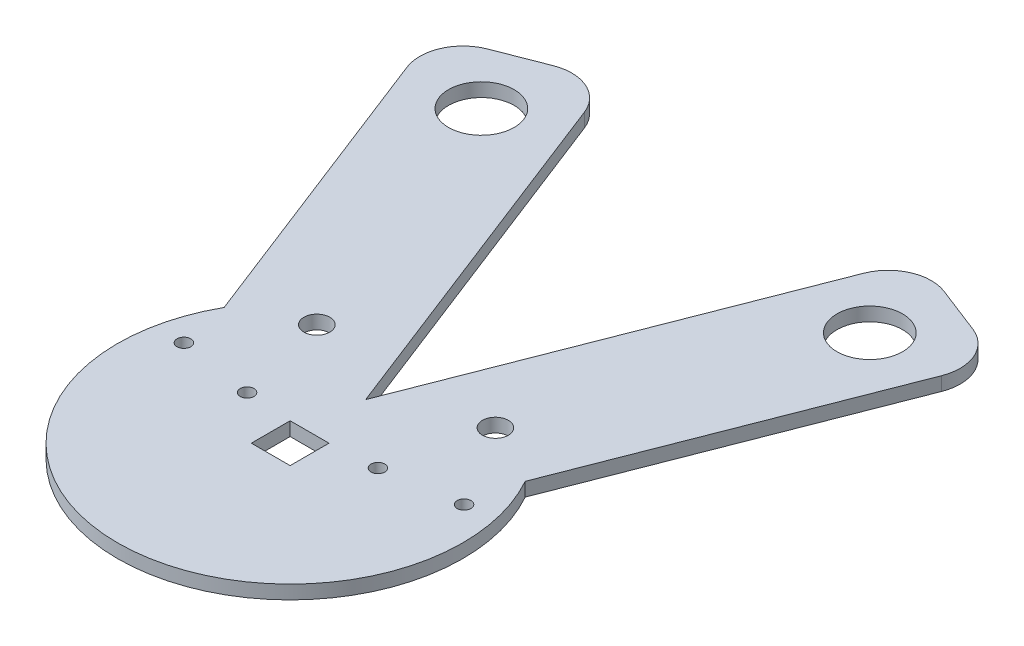
SolidWorks part; units mm, degrees
ref_plane "Front Plane" through (0, 0, 0) normal (0, 0, 1) x (1, 0, 0)
ref_plane "Top Plane" through (0, 0, 0) normal (0, 1, 0) x (1, 0, 0)
ref_plane "Right Plane" through (0, 0, 0) normal (1, 0, 0) x (0, 0, -1)
sketch "Sketch1" plane through (0, 0, 0) normal (0, 1, 0) x (1, 0, 0)
  line L0 (-45, 89.3029) -> (45, 89.3029) construction
  line L1 (-4.5, -4.5) -> (4.5, -4.5)
  line L2 (-4.5, -4.5) -> (-4.5, 4.5)
  line L3 (-4.5, 4.5) -> (4.5, 4.5)
  line L4 (4.5, -4.5) -> (4.5, 4.5)
  line L5 (-4.5, -4.5) -> (4.5, 4.5) construction
  line L6 (-4.5, 4.5) -> (4.5, -4.5) construction
  line L7 (-65.5537, 98.3347) -> (-23.6685, -9.2175)
  line L8 (23.6685, -9.2175) -> (65.5537, 98.3347)
  line L9 (-35.9681, 109.8566) -> (0, 17.4983)
  line L10 (0, 17.4983) -> (35.9681, 109.8566)
  line L11 (35.9681, 109.8566) -> (65.5537, 98.3347)
  line L12 (-65.5537, 98.3347) -> (-35.9681, 109.8566)
  line L13 (-51.0505, 104.8392) -> (-33.4783, 59.7176) construction
  line L14 (-4.9398, -38.9318) -> (18139.7128, 46552.608) construction
  line L15 (-32.4588, 7.8353) -> (-15.1612, 5.1816) construction
  line L16 (-20.6862, 26.8702) -> (-23.81, 6.5084) construction
  circle A0 centre (45, 89.3029) radius 7.6
  circle A1 centre (-45, 89.3029) radius 7.6
  arc A2 (23.6685, -9.2175) -> (-23.6685, -9.2175) centre (0, 0) cw
  circle A3 centre (-20.6862, 26.8702) radius 3
  circle A4 centre (-32.4588, 7.8353) radius 1.6
  circle A5 centre (-15.1612, 5.1816) radius 1.6
  arc A6 (-34.8821, 19.5765) -> (34.8821, 19.5765) centre (0, 0) ccw
  point P4 (0, 0)
  point P10 (0, 89.3029)
  point P19 (50.7609, 104.0957)
  point P20 (-50.7609, 104.0957)
  point P31 (-23.81, 6.5084)
  point P32 (-20.6862, 6.2702)
  point P33 (-23.6685, 6.49)
  dimension "D3" = 15.2
  dimension "D7" = 25.4
  dimension "D8" = 6
  dimension "D9" = 67
  dimension "D11" = 3.2
  dimension "D14" = 40
  dimension "D1" = 9
  dimension "D2" = 31.75
  dimension "D4" = 100
  dimension "D5" = 90
  dimension "D6" = 15.875
  dimension "D10" = 17.5
  dimension "D12" = 20.6
  dimension "D13" = 30
extrude "Boss-Extrude1" add sketch "Sketch1" along normal blind 3.175 contours A2 L8 L11 L10 L9 L12 L7 A5 A3 A1 A0 L4 L1 L2 L3 | L7 A6 L8 A2 A4 region at (-50.0773, 0, -102.3404) region at (-30.2048, 0, -4.8176)
fillet "Fillet1" radius 10 4 edges at (65.5537, 1.5875, -98.3347) (35.9681, 1.5875, -109.8566) (-35.9681, 1.5875, -109.8566) (-65.5537, 1.5875, -98.3347)
mirror "Mirror2" about plane through (0, 0, 0) normal (1, 0, 0) of face at (-32.4588, 3.175, -6.2353) of face at (-15.1612, 3.175, -3.5816) of face at (-20.6862, 3.175, -23.8702)
